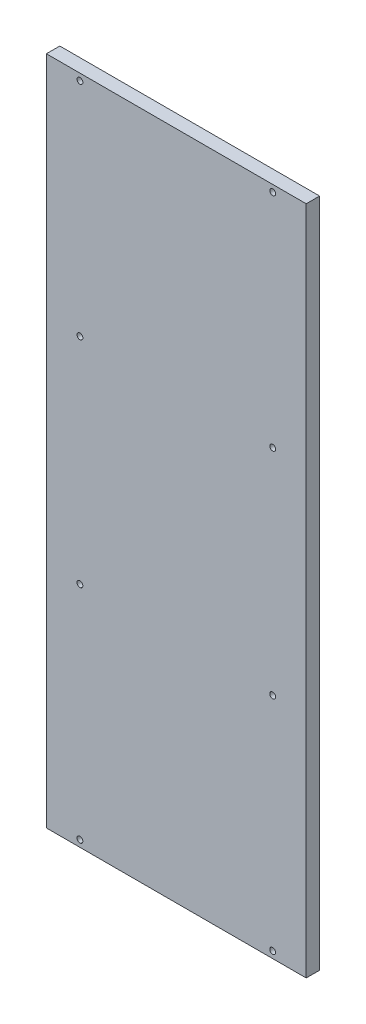
SolidWorks part; units mm, degrees
material "ДСП"
ref_plane "Спереди" through (0, 0, 0) normal (0, 0, 1) x (1, 0, 0)
ref_plane "Сверху" through (0, 0, 0) normal (0, 1, 0) x (1, 0, 0)
ref_plane "Справа" through (0, 0, 0) normal (1, 0, 0) x (0, 0, -1)
sketch "Эскиз1" plane through (0, 0, 0) normal (0, 0, 1) x (1, 0, 0)
  line L1 (0, 0) -> (310, 0)
  line L2 (0, 0) -> (0, 800)
  line L3 (0, 800) -> (310, 800)
  line L4 (310, 0) -> (310, 800)
  dimension "D1" = 800
  dimension "D2" = 310
extrude "Придание толщины" add sketch "Эскиз1" along normal blind 16
sketch "Эскиз3" plane through (0, 0, 16) normal (0, 0, 1) x (1, 0, 0)
  line L0 (0, 800) -> (0, 0) construction
  line L1 (0, 0) -> (310, 0) construction
  circle A0 centre (40, 8) radius 3.5
  dimension "D1" = 7
  dimension "D2" = 40
  dimension "D3" = 8
extrude "Отверстие 1" cut sketch "Эскиз3" against normal blind 16
sketch "Эскиз4" plane through (0, 0, 16) normal (0, 0, 1) x (1, 0, 0)
  line L0 (0, 800) -> (0, 0) construction
  line L1 (0, 0) -> (310, 0) construction
  circle A0 centre (270, 8) radius 3.5
  dimension "D3" = 7
  dimension "D1" = 270
  dimension "D2" = 8
extrude "Отверстие 2" cut sketch "Эскиз4" against normal blind 16
sketch "Эскиз5" plane through (0, 0, 16) normal (0, 0, 1) x (1, 0, 0)
  line L0 (0, 800) -> (0, 0) construction
  line L1 (0, 0) -> (310, 0) construction
  circle A0 centre (40, 792) radius 3.5
  dimension "D1" = 7
  dimension "D2" = 40
  dimension "D3" = 792
extrude "Отверстие 3" cut sketch "Эскиз5" against normal blind 16
sketch "Эскиз6" plane through (0, 0, 16) normal (0, 0, 1) x (1, 0, 0)
  line L0 (0, 800) -> (0, 0) construction
  line L1 (0, 0) -> (310, 0) construction
  circle A0 centre (270, 792) radius 3.5
  dimension "D1" = 7
  dimension "D3" = 792
  dimension "D2" = 270
extrude "Отверстие 4" cut sketch "Эскиз6" against normal blind 16
sketch "Эскиз7" plane through (0, 0, 16) normal (0, 0, 1) x (1, 0, 0)
  line L0 (0, 800) -> (0, 0) construction
  line L1 (0, 0) -> (310, 0) construction
  circle A0 centre (40, 272) radius 3.5
  dimension "D1" = 7
  dimension "D2" = 40
  dimension "D3" = 272
extrude "Отверстие 5" cut sketch "Эскиз7" against normal blind 16
sketch "Эскиз8" plane through (0, 0, 16) normal (0, 0, 1) x (1, 0, 0)
  line L0 (0, 800) -> (0, 0) construction
  line L1 (0, 0) -> (310, 0) construction
  circle A0 centre (270, 272) radius 3.5
  dimension "D1" = 7
  dimension "D2" = 270
  dimension "D3" = 272
extrude "Отверстие 6" cut sketch "Эскиз8" against normal blind 16
sketch "Эскиз9" plane through (0, 0, 16) normal (0, 0, 1) x (1, 0, 0)
  line L0 (0, 800) -> (0, 0) construction
  line L1 (0, 0) -> (310, 0) construction
  circle A0 centre (40, 528) radius 3.5
  dimension "D1" = 7
  dimension "D2" = 40
  dimension "D3" = 528
extrude "Отверстие 7" cut sketch "Эскиз9" against normal blind 16
sketch "Эскиз10" plane through (0, 0, 16) normal (0, 0, 1) x (1, 0, 0)
  line L0 (0, 800) -> (0, 0) construction
  line L1 (0, 0) -> (310, 0) construction
  circle A0 centre (270, 528) radius 3.5
  dimension "D1" = 7
  dimension "D2" = 270
  dimension "D3" = 528
extrude "Отверстие 8" cut sketch "Эскиз10" against normal blind 16
sketch "Эскиз27" plane through (0, 0, 16) normal (0, 0, 1) x (1, 0, 0)
  line L2 (0, 800) -> (0, 0) construction
  line L3 (0, 0) -> (310, 0) construction
  circle A0 centre (0, 0) radius 4
  dimension "D3" = 0
  dimension "D1" = 8
extrude "Отверстие 9" [suppressed] cut sketch "Эскиз27" against normal blind 10
sketch "Эскиз29" plane through (0, 0, 16) normal (0, 0, 1) x (1, 0, 0)
  line L2 (0, 800) -> (0, 0) construction
  line L3 (0, 0) -> (310, 0) construction
  circle A0 centre (0, 0) radius 4
  dimension "D1" = 8
extrude "Отверстие 10" [suppressed] cut sketch "Эскиз29" against normal blind 10
sketch "Эскиз30" plane through (0, 0, 16) normal (0, 0, 1) x (1, 0, 0)
  line L1 (0, 0) -> (310, 0) construction
  line L3 (0, 800) -> (0, 0) construction
  circle A0 centre (0, 0) radius 4
  dimension "D1" = 8
extrude "Отверстие 11" [suppressed] cut sketch "Эскиз30" against normal blind 10
sketch "Эскиз31" plane through (0, 0, 16) normal (0, 0, 1) x (1, 0, 0)
  line L2 (0, 0) -> (310, 0) construction
  line L3 (0, 800) -> (0, 0) construction
  circle A0 centre (0, 0) radius 4
  dimension "D1" = 8
extrude "Отверстие 12" [suppressed] cut sketch "Эскиз31" against normal blind 10
sketch "Эскиз11" plane through (0, 800, 0) normal (0, 1, 0) x (1, 0, 0)
  line L0 (0, -16) -> (0, 0) construction
  line L1 (310, -16) -> (0, -16) construction
  circle A0 centre (0, -16) radius 2.5
  dimension "D1" = 5
  dimension "D3" = 0
extrude "Отверстие А1" [suppressed] cut sketch "Эскиз11" against normal blind 37
sketch "Эскиз12" plane through (0, 800, 0) normal (0, 1, 0) x (1, 0, 0)
  line L1 (0, -16) -> (0, 0) construction
  line L2 (310, -16) -> (0, -16) construction
  circle A0 centre (0, -16) radius 2.5
  dimension "D1" = 5
  dimension "D3" = 0
extrude "Отверстие А2" [suppressed] cut sketch "Эскиз12" against normal blind 37
sketch "Эскиз13" plane through (0, 800, 0) normal (0, 1, 0) x (1, 0, 0)
  line L1 (0, -16) -> (0, 0) construction
  line L2 (310, -16) -> (0, -16) construction
  circle A0 centre (0, -16) radius 4
  dimension "D3" = 0
  dimension "D1" = 8
extrude "Отверстие А3" [suppressed] cut sketch "Эскиз13" against normal blind 20
sketch "Эскиз14" plane through (0, 800, 0) normal (0, 1, 0) x (1, 0, 0)
  line L0 (0, -16) -> (0, 0) construction
  line L1 (310, -16) -> (0, -16) construction
  circle A0 centre (0, -8) radius 4
  dimension "D3" = 8
  dimension "D1" = 8
extrude "Отверстие А4" [suppressed] cut sketch "Эскиз14" against normal blind 20
sketch "Эскиз15" plane through (310, 0, 0) normal (1, 0, 0) x (0, 0, -1)
  line L0 (-16, 800) -> (0, 800) construction
  line L1 (-16, 0) -> (-16, 800) construction
  circle A0 centre (-16, 800) radius 2.5
  dimension "D1" = 5
  dimension "D2" = 0
  dimension "D3" = 0
extrude "Отверстие В1" [suppressed] cut sketch "Эскиз15" against normal blind 37
sketch "Эскиз16" plane through (310, 0, 0) normal (1, 0, 0) x (0, 0, -1)
  line L0 (-16, 800) -> (0, 800) construction
  line L1 (-16, 0) -> (-16, 800) construction
  circle A0 centre (-16, 800) radius 2.5
  dimension "D1" = 5
extrude "Отверстие В2" [suppressed] cut sketch "Эскиз16" against normal blind 37
sketch "Эскиз17" plane through (310, 0, 0) normal (1, 0, 0) x (0, 0, -1)
  line L1 (-16, 800) -> (0, 800) construction
  line L2 (-16, 0) -> (-16, 800) construction
  circle A0 centre (-16, 800) radius 4
  dimension "D2" = 0
  dimension "D3" = 0
  dimension "D1" = 8
extrude "Отверстие В3" [suppressed] cut sketch "Эскиз17" against normal blind 20
sketch "Эскиз18" plane through (310, 0, 0) normal (1, 0, 0) x (0, 0, -1)
  line L0 (-16, 800) -> (0, 800) construction
  line L1 (-16, 0) -> (-16, 800) construction
  circle A0 centre (-16, 800) radius 4
  dimension "D2" = 8
  dimension "D3" = 0
  dimension "D1" = 0
extrude "Отверстие В4" [suppressed] cut sketch "Эскиз18" against normal blind 20
sketch "Эскиз19" plane through (0, 0, 0) normal (0, -1, 0) x (1, 0, 0)
  line L0 (310, 16) -> (310, 0) construction
  line L1 (0, 16) -> (310, 16) construction
  circle A0 centre (310, 16) radius 2.5
  dimension "D1" = 5
  dimension "D2" = 0
  dimension "D3" = 0
extrude "Отверстие С1" [suppressed] cut sketch "Эскиз19" against normal blind 37
sketch "Эскиз20" plane through (0, 0, 0) normal (0, -1, 0) x (1, 0, 0)
  line L0 (310, 16) -> (310, 0) construction
  line L1 (0, 16) -> (310, 16) construction
  circle A0 centre (310, 16) radius 2.5
  dimension "D3" = 0
  dimension "D1" = 0
  dimension "D2" = 5
extrude "Отверстие С2" [suppressed] cut sketch "Эскиз20" against normal blind 37
sketch "Эскиз21" plane through (0, 0, 0) normal (0, -1, 0) x (1, 0, 0)
  line L0 (310, 16) -> (310, 0) construction
  line L1 (0, 16) -> (310, 16) construction
  circle A0 centre (310, 16) radius 4
  dimension "D2" = 0
  dimension "D3" = 0
  dimension "D1" = 8
extrude "Отверстие С3" [suppressed] cut sketch "Эскиз21" against normal blind 20
sketch "Эскиз22" plane through (0, 0, 0) normal (0, -1, 0) x (1, 0, 0)
  line L0 (310, 16) -> (310, 0) construction
  line L1 (0, 16) -> (310, 16) construction
  circle A0 centre (310, 16) radius 4
  dimension "D2" = 0
  dimension "D3" = 0
  dimension "D1" = 8
extrude "Отверстие С4" [suppressed] cut sketch "Эскиз22" against normal blind 20
sketch "Эскиз23" plane through (0, 0, 0) normal (-1, 0, 0) x (0, 0, 1)
  line L0 (16, 0) -> (0, 0) construction
  line L1 (16, 800) -> (16, 0) construction
  circle A0 centre (16, 0) radius 2.5
  dimension "D1" = 5
  dimension "D2" = 0
  dimension "D3" = 0
extrude "Отверстие Д1" [suppressed] cut sketch "Эскиз23" against normal blind 37
sketch "Эскиз24" plane through (0, 0, 0) normal (-1, 0, 0) x (0, 0, 1)
  line L0 (16, 0) -> (0, 0) construction
  line L1 (16, 800) -> (16, 0) construction
  circle A0 centre (16, 0) radius 2.5
  dimension "D1" = 5
  dimension "D2" = 0
  dimension "D3" = 0
extrude "Отверстие Д2" [suppressed] cut sketch "Эскиз24" against normal blind 37
sketch "Эскиз25" plane through (0, 0, 0) normal (-1, 0, 0) x (0, 0, 1)
  line L0 (16, 0) -> (0, 0) construction
  line L1 (16, 800) -> (16, 0) construction
  circle A0 centre (16, 0) radius 4
  dimension "D2" = 0
  dimension "D3" = 0
  dimension "D1" = 8
extrude "Отверстие Д3" [suppressed] cut sketch "Эскиз25" against normal blind 20
sketch "Эскиз26" plane through (0, 0, 0) normal (-1, 0, 0) x (0, 0, 1)
  line L0 (16, 0) -> (0, 0) construction
  line L1 (16, 800) -> (16, 0) construction
  circle A0 centre (16, 0) radius 4
  dimension "D2" = 0
  dimension "D3" = 0
  dimension "D1" = 8
extrude "Отверстие Д4" [suppressed] cut sketch "Эскиз26" against normal blind 20
equation "\"D1@Придание толщины\" = \"Thick\""
equation "\"D2@Эскиз1\"=\"Width\""
equation "\"D1@Эскиз1\"=\"Height\""
equation "\"D1\" = 7"
equation "\"X1\" = 40"
equation "\"Y1\" = 8"
equation "\"H1\" = 16"
equation "\"D1@Эскиз3\"=\"D1\""
equation "\"D2@Эскиз3\"=\"X1\""
equation "\"D3@Эскиз3\"=\"Y1\""
equation "\"D1@Отверстие 1\"=\"H1\""
equation "\"D2\" = 7"
equation "\"X2\" = 270"
equation "\"Y2\" = 8"
equation "\"H2\" = 16"
equation "\"D3\" = 7"
equation "\"X3\" = 40"
equation "\"Y3\" = 792"
equation "\"H3\" = 16"
equation "\"D4\" = 7"
equation "\"X4\" = 270"
equation "\"Y4\" = 792"
equation "\"H4\" = 16"
equation "\"D5\" = 7"
equation "\"X5\" = 40"
equation "\"Y5\" = 272"
equation "\"H5\" = 16"
equation "\"D6\" = 7"
equation "\"X6\" = 270"
equation "\"Y6\" = 272"
equation "\"H6\" = 16"
equation "\"D7\" = 7"
equation "\"X7\" = 40"
equation "\"Y7\" = 528"
equation "\"H7\" = 16"
equation "\"D8\" = 7"
equation "\"X8\" = 270"
equation "\"Y8\" = 528"
equation "\"H8\" = 16"
equation "\"D3@Эскиз4\"=\"D2\""
equation "\"D1@Эскиз4\"=\"X2\""
equation "\"D2@Эскиз4\"=\"Y2\""
equation "\"D1@Отверстие 2\"=\"H2\""
equation "\"D2@Эскиз5\"=\"X3\""
equation "\"D1@Эскиз5\"=\"D3\""
equation "\"D3@Эскиз5\"=\"Y3\""
equation "\"D1@Отверстие 3\" = \"H3\""
equation "\"D1@Эскиз6\"=\"D4\""
equation "\"D2@Эскиз6\"=\"X4\""
equation "\"D3@Эскиз6\"=\"Y4\""
equation "\"D1@Отверстие 4\" = \"H4\""
equation "\"D1@Эскиз7\"=\"D5\""
equation "\"D2@Эскиз7\"=\"X5\""
equation "\"D3@Эскиз7\"=\"Y5\""
equation "\"D1@Отверстие 5\" = \"H5\""
equation "\"D1@Эскиз8\"=\"D6\""
equation "\"D2@Эскиз8\"=\"X6\""
equation "\"D3@Эскиз8\"=\"Y6\""
equation "\"D1@Отверстие 6\" = \"H6\""
equation "\"D1@Эскиз9\"=\"D7\""
equation "\"D2@Эскиз9\"=\"X7\""
equation "\"D3@Эскиз9\"=\"Y7\""
equation "\"D1@Отверстие 7\" = \"H7\""
equation "\"D1@Эскиз10\"=\"D8\""
equation "\"D2@Эскиз10\"=\"X8\""
equation "\"D3@Эскиз10\"=\"Y8\""
equation "\"D1@Отверстие 8\" = \"H8\""
equation "\"Отверстие 1\"= IIF ( \"D1\" = 0 , \"suppressed\" , \"unsuppressed\" )"
equation "\"Отверстие 2\"= IIF ( \"D2\" = 0 , \"suppressed\" , \"unsuppressed\" )"
equation "\"Отверстие 3\"= IIF ( \"D3\" = 0 , \"suppressed\" , \"unsuppressed\" )"
equation "\"Отверстие 4\"= IIF ( \"D4\" = 0 , \"suppressed\" , \"unsuppressed\" )"
equation "\"Отверстие 5\"= IIF ( \"D5\" = 0 , \"suppressed\" , \"unsuppressed\" )"
equation "\"Отверстие 6\" = IIF ( \"D6\" = 0 , \"suppressed\" , \"unsuppressed\" )"
equation "\"Отверстие 7\"= IIF ( \"D7\" = 0 , \"suppressed\" , \"unsuppressed\" )"
equation "\"Отверстие 8\"= IIF ( \"D8\" = 0 , \"suppressed\" , \"unsuppressed\" )"
equation "\"DA1\" = 0"
equation "\"XA1\" = 0"
equation "\"YA1\" = 0"
equation "\"HA1\" = 0"
equation "\"DA2\" = 0"
equation "\"XA2\" = 0"
equation "\"YA2\" = 0"
equation "\"HA2\" = 0"
equation "\"DA3\" = 0"
equation "\"XA3\" = 0"
equation "\"YA3\" = 0"
equation "\"DA4\" = 0"
equation "\"XA4\" = 0"
equation "\"YA4\" = 0"
equation "\"HA4\" = 0"
equation "\"D1@Эскиз11\"=\"DA1\""
equation "\"D2@Эскиз11\"=\"XA1\""
equation "\"D3@Эскиз11\"=\"YA1\""
equation "\"D1@Отверстие А1\" = \"HA1\""
equation "\"D1@Эскиз12\"=\"DA2\""
equation "\"D2@Эскиз12\"=\"XA2\""
equation "\"HA3\" = 0"
equation "\"D1@Эскиз13\"=\"DA3\""
equation "\"D2@Эскиз13\"=\"XA3\""
equation "\"D3@Эскиз13\"=\"YA3\""
equation "\"D1@Отверстие А3\" = \"HA3\""
equation "\"D1@Отверстие А2\" = \"HA2\""
equation "\"D1@Эскиз14\"=\"DA4\""
equation "\"D2@Эскиз14\"=\"XA4\""
equation "\"Отверстие А1\"= IIF ( \"DA1\" = 0 , \"suppressed\" , \"unsuppressed\" )"
equation "\"Отверстие А2\"= IIF ( \"DA2\" = 0 , \"suppressed\" , \"unsuppressed\" )"
equation "\"Отверстие А3\"= IIF ( \"DA3\" = 0 , \"suppressed\" , \"unsuppressed\" )"
equation "\"Отверстие А4\"= IIF ( \"DA4\" = 0 , \"suppressed\" , \"unsuppressed\" )"
equation "\"DB1\" = 0"
equation "\"XB1\" = 0"
equation "\"YB1\" = 0"
equation "\"HB1\" = 0"
equation "\"DB2\" = 0"
equation "\"XB2\" = 0"
equation "\"YB2\" = 0"
equation "\"HB2\" = 0"
equation "\"DB3\" = 0"
equation "\"XB3\" = 0"
equation "\"YB3\" = 0"
equation "\"HB3\" = 0"
equation "\"DB4\" = 0"
equation "\"XB4\" = 0"
equation "\"YB4\" = 0"
equation "\"HB4\" = 0"
equation "\"DC1\" = 0"
equation "\"XC1\" = 0"
equation "\"YC1\" = 0"
equation "\"HC1\" = 0"
equation "\"DC2\" = 0"
equation "\"XC2\" = 0"
equation "\"YC2\" = 0"
equation "\"HC2\" = 0"
equation "\"DC3\" = 0"
equation "\"XC3\" = 0"
equation "\"YC3\" = 0"
equation "\"HC3\" = 0"
equation "\"DC4\" = 0"
equation "\"XC4\" = 0"
equation "\"YC4\" = 0"
equation "\"HC4\" = 0"
equation "\"DD1\" = 0"
equation "\"XD1\" = 0"
equation "\"YD1\" = 0"
equation "\"HD1\" = 0"
equation "\"DD2\" = 0"
equation "\"XD2\" = 0"
equation "\"YD2\" = 0"
equation "\"HD2\" = 0"
equation "\"DD3\" = 0"
equation "\"XD3\" = 0"
equation "\"YD3\" = 0"
equation "\"HD3\" = 0"
equation "\"DD4\" = 0"
equation "\"XD4\" = 0"
equation "\"YD4\" = 0"
equation "\"HD4\" = 0"
equation "\"D1@Эскиз15\"=\"DB1\""
equation "\"D2@Эскиз15\"=\"XB1\""
equation "\"D3@Эскиз15\"=\"YB1\""
equation "\"D1@Отверстие В1\" = \"HB1\""
equation "\"D1@Эскиз16\"=\"DB2\""
equation "\"D2@Эскиз16\"=\"XB2\""
equation "\"D3@Эскиз16\"=\"YB2\""
equation "\"D1@Отверстие В2\" = \"HB2\""
equation "\"D1@Эскиз17\"=\"DB3\""
equation "\"D2@Эскиз17\"=\"XB3\""
equation "\"D3@Эскиз17\"=\"YB3\""
equation "\"D1@Отверстие В3\" = \"HB3\""
equation "\"D1@Эскиз18\"=\"XB4\""
equation "\"D2@Эскиз18\"=\"DB4\""
equation "\"D3@Эскиз18\"=\"YB4\""
equation "\"D1@Отверстие В4\" = \"HB4\""
equation "\"D1@Эскиз19\"=\"DC1\""
equation "\"D2@Эскиз19\"=\"XC1\""
equation "\"D3@Эскиз19\"=\"YC1\""
equation "\"D1@Отверстие С1\" = \"HC1\""
equation "\"D1@Эскиз20\"=\"XC2\""
equation "\"D2@Эскиз20\"=\"DC2\""
equation "\"D3@Эскиз20\"=\"YC2\""
equation "\"D1@Отверстие С2\" = \"HC2\""
equation "\"D1@Эскиз21\"=\"DC3\""
equation "\"D2@Эскиз21\"=\"XC3\""
equation "\"D3@Эскиз21\"=\"YC3\""
equation "\"D1@Отверстие С3\" = \"HC3\""
equation "\"D1@Эскиз22\"=\"DC4\""
equation "\"D2@Эскиз22\"=\"XC4\""
equation "\"D3@Эскиз22\"=\"YC4\""
equation "\"D1@Отверстие С4\" = \"HC4\""
equation "\"D1@Эскиз23\"=\"DD1\""
equation "\"D2@Эскиз23\"=\"XD1\""
equation "\"D3@Эскиз23\"=\"YD1\""
equation "\"D1@Отверстие Д1\" = \"HD1\""
equation "\"D1@Эскиз24\"=\"DD2\""
equation "\"D2@Эскиз24\"=\"XD2\""
equation "\"D3@Эскиз24\"=\"YD2\""
equation "\"D1@Отверстие Д2\" = \"HD2\""
equation "\"D1@Эскиз25\"=\"DD3\""
equation "\"D2@Эскиз25\"=\"XD3\""
equation "\"D3@Эскиз25\"=\"YD3\""
equation "\"D1@Отверстие Д3\" = \"HD3\""
equation "\"D1@Эскиз26\"=\"DD4\""
equation "\"D2@Эскиз26\"=\"XD4\""
equation "\"D3@Эскиз26\"=\"YD4\""
equation "\"D1@Отверстие Д4\" = \"HD4\""
equation "\"Отверстие В1\"= IIF ( \"DB1\" = 0 , \"suppressed\" , \"unsuppressed\" )"
equation "\"Отверстие В2\"= IIF ( \"DB2\" = 0 , \"suppressed\" , \"unsuppressed\" )"
equation "\"Отверстие В3\"= IIF ( \"DB3\" = 0 , \"suppressed\" , \"unsuppressed\" )"
equation "\"Отверстие В4\"= IIF ( \"DB4\" = 0 , \"suppressed\" , \"unsuppressed\" )"
equation "\"Отверстие С1\"= IIF ( \"DC1\" = 0 , \"suppressed\" , \"unsuppressed\" )"
equation "\"Отверстие С2\"= IIF ( \"DC2\" = 0 , \"suppressed\" , \"unsuppressed\" )"
equation "\"Отверстие С3\"= IIF ( \"DC3\" = 0 , \"suppressed\" , \"unsuppressed\" )"
equation "\"Отверстие С4\"= IIF ( \"DC4\" = 0 , \"suppressed\" , \"unsuppressed\" )"
equation "\"Отверстие Д1\"= IIF ( \"DD1\" = 0 , \"suppressed\" , \"unsuppressed\" )"
equation "\"Отверстие Д2\"= IIF ( \"DD2\" = 0 , \"suppressed\" , \"unsuppressed\" )"
equation "\"Отверстие Д3\"= IIF ( \"DD3\" = 0 , \"suppressed\" , \"unsuppressed\" )"
equation "\"Отверстие Д4\"= IIF ( \"DD4\" = 0 , \"suppressed\" , \"unsuppressed\" )"
equation "\"D9\" = 0"
equation "\"X9\" = 0"
equation "\"Y9\" = 0"
equation "\"H9\" = 0"
equation "\"D10\" = 0"
equation "\"X10\" = 0"
equation "\"Y10\" = 0"
equation "\"H10\" = 0"
equation "\"D11\" = 0"
equation "\"X11\" = 0"
equation "\"Y11\" = 0"
equation "\"H11\" = 0"
equation "\"D12\" = 0"
equation "\"X12\" = 0"
equation "\"Y12\" = 0"
equation "\"H12\" = 0"
equation "\"D1@Эскиз27\"=\"D9\""
equation "\"D2@Эскиз27\"=\"X9\""
equation "\"D3@Эскиз27\"=\"Y9\""
equation "\"D1@Отверстие 9\" = \"H9\""
equation "\"D1@Эскиз29\"=\"D10\""
equation "\"D2@Эскиз29\"=\"X10\""
equation "\"D3@Эскиз29\"=\"Y10\""
equation "\"D1@Отверстие 10\" = \"H10\""
equation "\"D1@Эскиз30\"=\"D11\""
equation "\"D2@Эскиз30\"=\"X11\""
equation "\"D3@Эскиз30\"=\"Y11\""
equation "\"D1@Отверстие 11\" = \"H11\""
equation "\"D1@Эскиз31\"=\"D12\""
equation "\"D2@Эскиз31\"=\"X12\""
equation "\"D3@Эскиз31\"=\"Y12\""
equation "\"D1@Отверстие 12\" = \"H12\""
equation "\"Отверстие 9\"= IIF ( \"D9\" = 0 , \"suppressed\" , \"unsuppressed\" )"
equation "\"Отверстие 10\"= IIF ( \"D10\" = 0 , \"suppressed\" , \"unsuppressed\" )"
equation "\"Отверстие 11\"= IIF ( \"D11\" = 0 , \"suppressed\" , \"unsuppressed\" )"
equation "\"Отверстие 12\"= IIF ( \"D12\" = 0 , \"suppressed\" , \"unsuppressed\" )"
equation "\"Height\" = 800"
equation "\"Width\" = 310"
equation "\"Thick\" = 16"
equation "\"D3@Эскиз12\"=\"YA2\""
